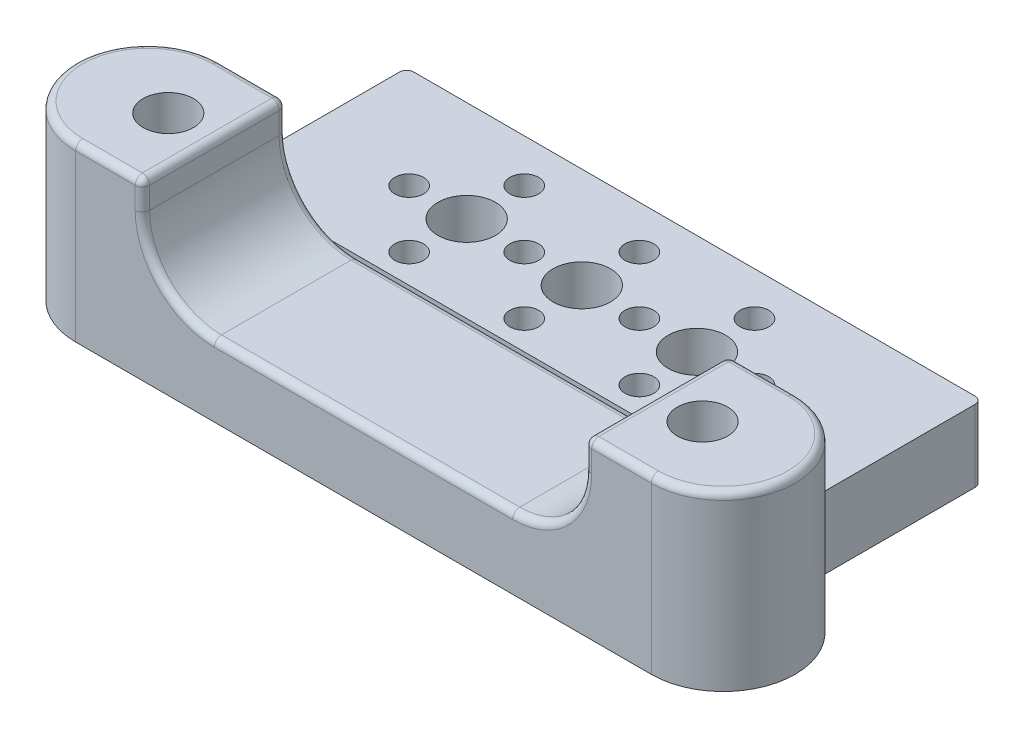
SolidWorks part; units mm, degrees
ref_plane "Front Plane" through (0, 0, 0) normal (0, 0, 1) x (1, 0, 0)
ref_plane "Top Plane" through (0, 0, 0) normal (0, 1, 0) x (1, 0, 0)
ref_plane "Right Plane" through (0, 0, 0) normal (1, 0, 0) x (0, 0, -1)
sketch "Sketch1" plane through (0, 0, 0) normal (0, 1, 0) x (1, 0, 0)
  line L0 (40, -10) -> (-40, -10)
  line L1 (40, -10) -> (40, 10)
  line L2 (-40, -10) -> (-40, 10)
  line L3 (40, 10) -> (-40, 10)
  line L4 (40, -10) -> (-40, 10) construction
  line L5 (-40, -10) -> (40, 10) construction
  arc A0 (-40, 10) -> (-40, -10) centre (-40, 0) ccw
  arc A1 (40, 10) -> (40, -10) centre (40, 0) cw
  point P1 (0, 0)
  dimension "D1" = 80
  dimension "D2" = 20
extrude "Boss-Extrude1" add sketch "Sketch1" along normal blind 10 contours L1 L3 L2 L0 | L2 A0 | A1 L1 region at (0, 0, 0) region at (44.2441, 0, 0) region at (-44.2441, 0, 0)
sketch "Sketch2" plane through (0, 10, 0) normal (0, 1, 0) x (1, 0, 0)
  circle A0 centre (-37.125, 0) radius 3.5
  circle A1 centre (37.125, 0) radius 3.5
  dimension "D1" = 7
  dimension "D2" = 7
  dimension "D3" = 74.25
  dimension "D4" = 37.125
extrude "Cut-Extrude1" cut sketch "Sketch2" against normal blind 10
sketch "Sketch3" plane through (0, 10, 0) normal (0, 1, 0) x (1, 0, 0)
  line L0 (40, -10) -> (-40, -10) construction
  line L1 (-40, 10) -> (-30.7265, 10)
  line L2 (-40, 10) -> (-40, -10)
  line L3 (-40, -10) -> (-30.7265, -10)
  line L4 (-30.7265, 10) -> (-30.7265, -10)
  arc A0 (-40, 10) -> (-40, -10) centre (-40, 0) ccw
  circle M2 centre (-37.125, 0) radius 3.5
  line M3 (-40, -10) -> (40, -10)
  line M5 (40, 10) -> (-40, 10)
  arc M6 (-40, 10) -> (-40, -10) centre (-40, 0) ccw
extrude "Boss-Extrude2" add sketch "Sketch3" along normal blind 14 contours L2 M6 M2 | L4 L2 M5 M2 M3 region at (-35.3633, 10, -9.7795) region at (-44.2877, 10, 0)
mirror "Mirror1" about plane through (0, 0, 0) normal (1, 0, 0) of "Boss-Extrude2"
fillet "Fillet1" radius 10 2 edges at (30.7265, 10, 0)
fillet "Fillet2" radius 1 18 edges at (30.7265, 22, -10) (27.7976, 12.9289, -10) (-27.7976, 12.9289, -10) (30.7265, 22, 10) (27.7976, 12.9289, 10) (35.3633, 24, -10) (35.3633, 24, 10) (-35.3633, 24, -10) (-35.3633, 24, 10) (-27.7976, 12.9289, 10) (-30.7265, 24, 0) (30.7265, 24, 0) (50, 24, 0) (-50, 24, 0)
sketch "Sketch4" plane through (0, 0, 0) normal (0, 1, 0) x (1, 0, 0)
  line L0 (-40, 10) -> (40, 10)
  line L1 (-40, 10) -> (-40, 36)
  line L2 (40, 10) -> (40, 36)
  line L3 (-40, 36) -> (40, 36)
  dimension "D1" = 26
extrude "Boss-Extrude3" add sketch "Sketch4" along normal blind 10
fillet "Fillet6" radius 1 4 edges at (-40, 5, -10) (40, 5, -10) (40, 5, -36) (-40, 5, -36)
sketch "Sketch5" plane through (0, 10, 0) normal (0, 1, 0) x (1, 0, 0)
  line L0 (-40, 10) -> (-25.3091, 10) construction
  line L1 (6.3454, 22) -> (6.3454, 36)
  line L2 (-25.3091, 10) -> (25.3091, 10) construction
  line L3 (-9.6546, 10) -> (-9.6546, 36)
  line L4 (39, 36) -> (-39, 36) construction
  circle A0 centre (-17.6546, 22) radius 4
  circle A1 centre (-9.6546, 22) radius 2
  circle A2 centre (-17.6546, 14) radius 2
  circle A3 centre (-25.6546, 22) radius 2
  circle A4 centre (-17.6546, 30) radius 2
  circle A7 centre (-1.6546, 30) radius 2
  circle A8 centre (6.3454, 22) radius 2
  circle A9 centre (-1.6546, 14) radius 2
  circle A10 centre (-1.6546, 22) radius 4
  circle A11 centre (22.3454, 22) radius 2
  circle A12 centre (14.3454, 14) radius 2
  circle A13 centre (14.3454, 30) radius 2
  circle A14 centre (14.3454, 22) radius 4
  point P4 (-32.6546, 10)
  point P18 (-17.6546, 22)
  point P27 (-17.6546, 22)
  dimension "D2" = 8
  dimension "D4" = 4
  dimension "D1" = 15
  dimension "D3" = 12
  dimension "D5" = 8
  dimension "D6" = 4
extrude "Cut-Extrude2" cut sketch "Sketch5" against normal blind 10 contours A0 | A4 | A2 | L3 A1 | L3 A1 | A3 | A9 | A10 | A8 | A7 | A13 | A14 | A11 | A12 region at (-10.5034, 10, -22) region at (-8.8057, 10, -22) region at (-17.6546, 10, -22) region at (-17.6546, 10, -14) region at (-25.6546, 10, -22) region at (-17.6546, 10, -30) region at (-1.6546, 10, -30) region at (4.9712, 10, -20.6258) region at (-1.6546, 10, -14) region at (-1.6546, 10, -22) region at (22.3454, 10, -22) region at (14.3454, 10, -14) region at (14.3454, 10, -30) region at (14.3454, 10, -22)
